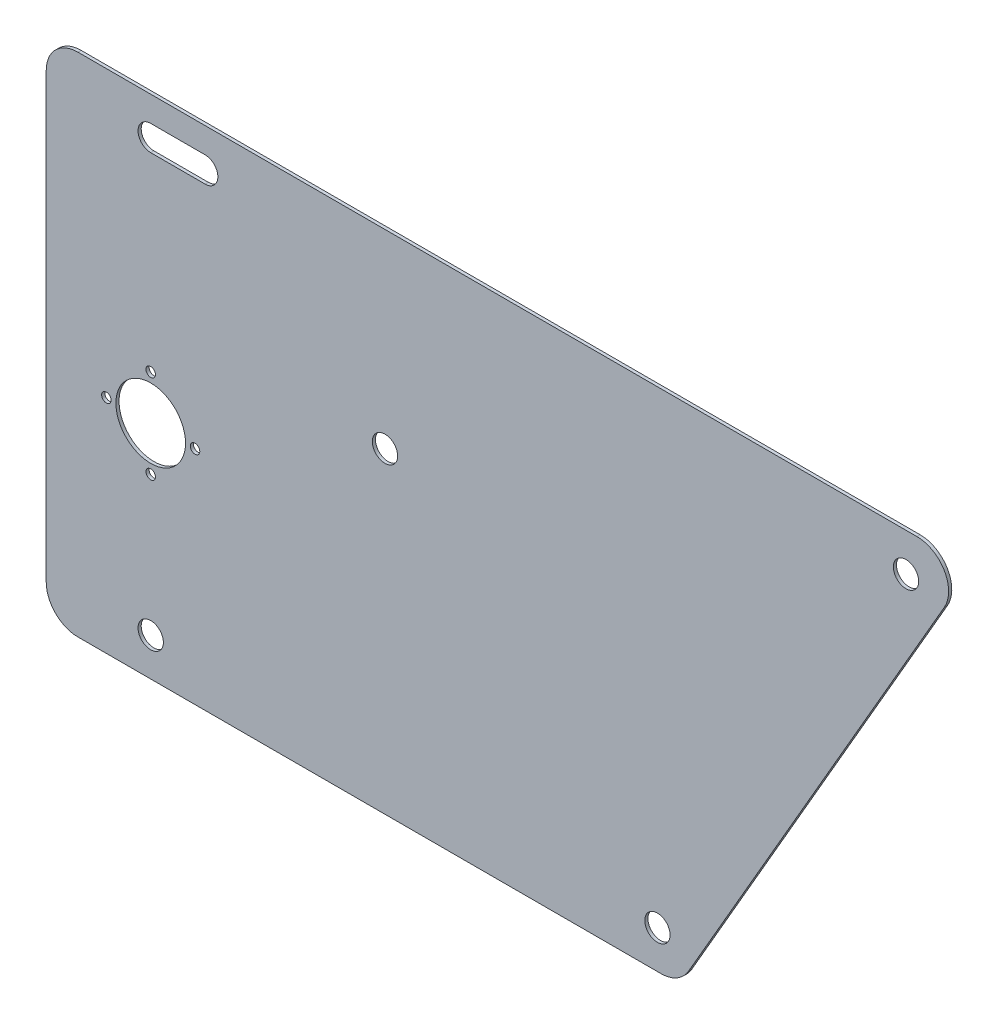
SolidWorks part; units mm, degrees
ref_plane "Front Plane" through (0, 0, 0) normal (0, 0, 1) x (1, 0, 0)
ref_plane "Top Plane" through (0, 0, 0) normal (0, 1, 0) x (1, 0, 0)
ref_plane "Right Plane" through (0, 0, 0) normal (1, 0, 0) x (0, 0, -1)
sketch "Sketch1" plane through (0, 0, 0) normal (0, 0, 1) x (1, 0, 0)
  line L0 (100, 80) -> (192.376, 80)
  line L1 (-100, -80) -> (100, -80)
  line L2 (-100, -80) -> (-100, 80)
  line L3 (-100, 80) -> (100, 80)
  line L4 (100, -80) -> (100, 80)
  line L5 (-100, -80) -> (100, 80) construction
  line L6 (-100, 80) -> (100, -80) construction
  line L7 (192.376, 80) -> (100, -80)
  line L8 (100, 80) -> (100, -80)
  point P0 (0, 0)
  dimension "D1" = 160
  dimension "D2" = 200
  dimension "D3" = 30
extrude "Boss-Extrude1" add sketch "Sketch1" along normal blind 1 contours L1 L4 L3 L2 | L7 L0 L4 region at (0, 0, 0) region at (130.792, 26.6667, 0)
fillet "Fillet1" radius 10 4 edges at (192.376, 80, 0.5) (100, -80, 0.5) (-100, -80, 0.5) (-100, 80, 0.5)
sketch "Sketch2" plane through (0, 0, 1) normal (0, 0, 1) x (1, 0, 0)
  line L0 (-90, -80) -> (94.2265, -80) construction
  line L1 (183.7158, 65) -> (102.8868, -75) construction
  line L2 (-90, 80) -> (175.0555, 80) construction
  line L4 (-67, 68) -> (-49.7837, 68) construction
  line L7 (-100, -70) -> (-100, 70) construction
  line L9 (-67, 72) -> (-49.7837, 72)
  line L10 (-67, 64) -> (-49.7837, 64)
  circle A0 centre (93.0718, -68) radius 4
  circle A1 centre (171.5914, 68) radius 4
  circle A2 centre (-67, -10) radius 11
  circle A3 centre (-67, -68) radius 4
  circle A4 centre (-53, -10) radius 1.5
  circle A5 centre (-67, 4) radius 1.5
  circle A6 centre (-81, -10) radius 1.5
  circle A7 centre (-67, -24) radius 1.5
  circle A10 centre (6.9988, 20) radius 4
  arc A11 (-67, 72) -> (-67, 64) centre (-67, 68) ccw
  arc A12 (-49.7837, 64) -> (-49.7837, 72) centre (-49.7837, 68) ccw
  point P12 (-58.3919, 68)
  point P29 (0, 0)
  point P30 (0, 0)
  point P33 (14.4407, -5)
  point P36 (-7.8849, 30)
  point P37 (6.9988, 30)
  dimension "D3" = 8
  dimension "D4" = 8
  dimension "D9" = 22
  dimension "D10" = 8
  dimension "D12" = 3
  dimension "D13" = 3
  dimension "D14" = 3
  dimension "D15" = 3
  dimension "D16" = 14
  dimension "D20" = 4
  dimension "D22" = 8
  dimension "D1" = 12
  dimension "D2" = 12
  dimension "D5" = 12
  dimension "D6" = 12
  dimension "D7" = 33
  dimension "D8" = 70
  dimension "D11" = 12
  dimension "D17" = 14
  dimension "D18" = 14
  dimension "D19" = 14
  dimension "D24" = 60
extrude "Cut-Extrude1" cut sketch "Sketch2" against normal blind 3
